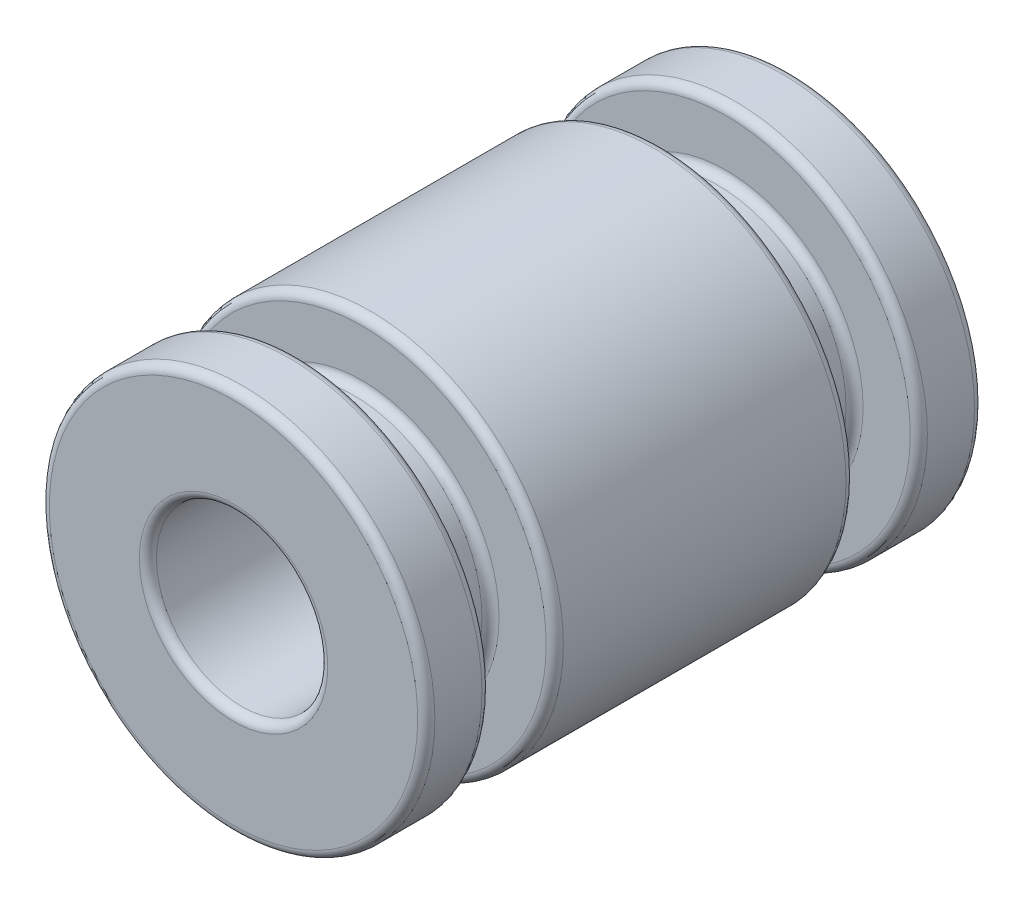
SolidWorks part; units mm, degrees
ref_plane "Front Plane" through (0, 0, 0) normal (0, 0, 1) x (1, 0, 0)
ref_plane "Top Plane" through (0, 0, 0) normal (0, 1, 0) x (1, 0, 0)
ref_plane "Right Plane" through (0, 0, 0) normal (1, 0, 0) x (0, 0, -1)
sketch "Sketch1" plane through (0, 0, 0) normal (0, 1, 0) x (1, 0, 0)
  line L0 (2, 6.3) -> (2, -6.3)
  line L1 (2.2, -6.5) -> (4.3, -6.5)
  line L2 (4.5, -6.3) -> (4.5, -5.2)
  line L3 (4.3, -5) -> (3.2, -5)
  line L4 (3, -4.8) -> (3, -3.7)
  line L5 (3.2, -3.5) -> (4.3, -3.5)
  line L6 (4.5, -3.3) -> (4.5, 3.3)
  line L7 (4.3, 3.5) -> (3.2, 3.5)
  line L8 (3, 3.7) -> (3, 4.8)
  line L9 (3.2, 5) -> (4.3, 5)
  line L10 (4.5, 5.2) -> (4.5, 6.3)
  line L11 (4.3, 6.5) -> (2.2, 6.5)
  line L12 (0, 6.503) -> (0, -6.503) construction
  arc A0 (2.2, 6.5) -> (2, 6.3) centre (2.2, 6.3) ccw
  arc A1 (2, -6.3) -> (2.2, -6.5) centre (2.2, -6.3) ccw
  arc A2 (4.3, -6.5) -> (4.5, -6.3) centre (4.3, -6.3) ccw
  arc A3 (4.5, -5.2) -> (4.3, -5) centre (4.3, -5.2) ccw
  arc A4 (3.2, -5) -> (3, -4.8) centre (3.2, -4.8) cw
  arc A5 (3, -3.7) -> (3.2, -3.5) centre (3.2, -3.7) cw
  arc A6 (4.3, -3.5) -> (4.5, -3.3) centre (4.3, -3.3) ccw
  arc A7 (4.5, 3.3) -> (4.3, 3.5) centre (4.3, 3.3) ccw
  arc A8 (3.2, 3.5) -> (3, 3.7) centre (3.2, 3.7) cw
  arc A9 (3, 4.8) -> (3.2, 5) centre (3.2, 4.8) cw
  arc A10 (4.3, 5) -> (4.5, 5.2) centre (4.3, 5.2) ccw
  arc A11 (4.5, 6.3) -> (4.3, 6.5) centre (4.3, 6.3) ccw
revolve "Revolve1" add sketch "Sketch1" angle 360 about L12 reverse direction yes
